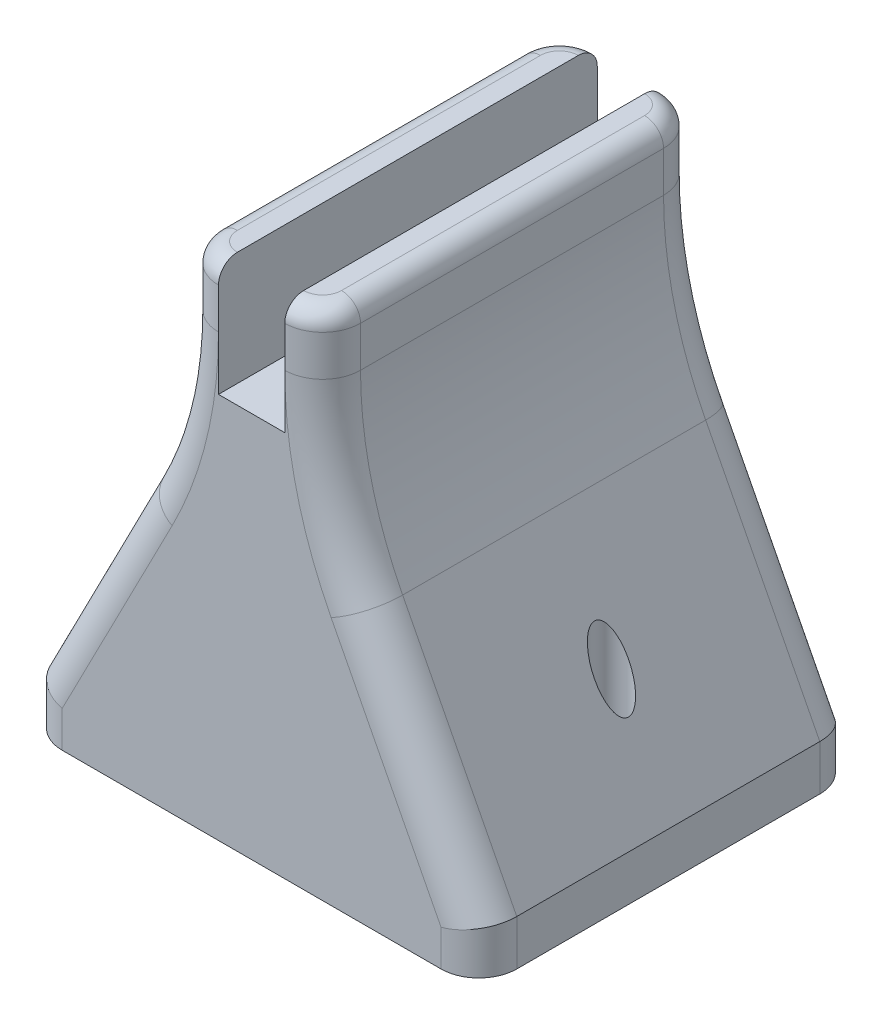
SolidWorks part; units mm, degrees
ref_plane "Front Plane" through (0, 0, 0) normal (0, 0, 1) x (1, 0, 0)
ref_plane "Top Plane" through (0, 0, 0) normal (0, 1, 0) x (1, 0, 0)
ref_plane "Right Plane" through (0, 0, 0) normal (1, 0, 0) x (0, 0, -1)
sketch "Sketch1" plane through (0, 0, 0) normal (0, 0, 1) x (1, 0, 0)
  line L0 (0, 0) -> (-37.5, 0)
  line L1 (-37.5, 0) -> (-37.5, 40)
  line L2 (-37.5, 40) -> (-27.5, 40)
  line L3 (-27.5, 40) -> (-27.5, 10)
  line L4 (-27.5, 10) -> (-10, 10)
  line L5 (-10, 10) -> (-10, 40)
  line L6 (-10, 40) -> (0, 40)
  line L7 (0, 40) -> (0, 0)
  dimension "D1" = 10
  dimension "D2" = 10
  dimension "D3" = 10
  dimension "D4" = 17.5
  dimension "D5" = 30
  dimension "D6" = 30
extrude "Boss-Extrude1" add sketch "Sketch1" along normal blind 100
sketch "Sketch2" plane through (0, 0, 0) normal (0, -1, 0) x (1, 0, 0)
  line L0 (-37.5, 100) -> (0, 0) construction
  line L1 (0, 100) -> (-37.5, 0) construction
  line L2 (-37.5, 100) -> (0, 100) construction
  line L3 (-78.75, 100) -> (41.25, 100)
  line L4 (-78.75, 100) -> (-78.75, 0)
  line L5 (-78.75, 0) -> (41.25, 0)
  line L6 (41.25, 100) -> (41.25, 0)
  line L7 (-78.75, 100) -> (41.25, 0) construction
  line L8 (-78.75, 0) -> (41.25, 100) construction
  point P8 (-18.75, 50)
  dimension "D1" = 0
  dimension "D2" = 120
extrude "Boss-Extrude2" add sketch "Sketch2" along normal blind 92
sketch "Sketch3" plane through (0, 0, 0) normal (0, 1, 0) x (1, 0, 0)
  line L0 (41.25, 0) -> (41.25, -100) construction
  line L1 (41.25, -100) -> (0, -100) construction
  line L2 (-37.5, -100) -> (-78.75, -100) construction
  line L3 (-78.75, -100) -> (-78.75, 0) construction
  circle A0 centre (26.25, -50) radius 4.5
  circle A1 centre (-63.75, -50) radius 4.5
  point P0 (26.25, -50)
  point P1 (-63.75, -50)
  dimension "D5" = 9
  dimension "D6" = 9
  dimension "D1" = 15
  dimension "D2" = 50
  dimension "D3" = 50
  dimension "D4" = 15
extrude "Cut-Extrude1" cut sketch "Sketch3" against normal blind 85
sketch "Sketch4" plane through (0, -85, 0) normal (0, 1, 0) x (1, 0, 0)
  circle A0 centre (26.25, -50) radius 2.65
  circle A1 centre (-63.75, -50) radius 2.65
  dimension "D1" = 5.3
  dimension "D2" = 5.3
extrude "Cut-Extrude2" cut sketch "Sketch4" against normal up to surface (7 mm away) up to face at (-18.75, -92, 50)
sketch "Sketch5" plane through (0, 0, 0) normal (0, 0, -1) x (-1, 0, 0)
  line L0 (0, 0) -> (-41.25, -80)
  line L1 (-41.25, -92) -> (-41.25, 0) construction
  line L2 (-41.25, -80) -> (-41.25, 0)
  line L3 (-41.25, 0) -> (0, 0)
  line L4 (37.5, 0) -> (78.75, 0)
  line L8 (78.75, 0) -> (78.75, -80)
  line L9 (78.75, -92) -> (78.75, 0) construction
  line L10 (78.75, -80) -> (37.5, 0)
  dimension "D1" = 41.25
  dimension "D2" = 41.25
  dimension "D3" = 80
  dimension "D4" = 80
extrude "Cut-Extrude3" cut sketch "Sketch5" against normal up to surface (100 mm away) up to face at (-18.75, -0.3333, 100)
fillet "Fillet1" radius 100 1 edges at (0, 0, 50) type face fillet first side face at (0, 20, 50) second side face at (20.625, -40, 50)
fillet "Fillet2" radius 100 1 edges at (-37.5, 0, 50) type face fillet first side face at (-37.5, 20, 50) second side face at (-58.125, -40, 50)
fillet "Fillet4" radius 10 16 edges at (-37.5, 32.1317, 100) (-40.3197, 0.6842, 100) (-37.5, 32.1317, 0) (-40.3197, 0.6842, 0) (-63.6848, -50.7827, 100) (-63.6848, -50.7827, 0) (0, 32.1317, 0) (2.8197, 0.6842, 0) (0, 32.1317, 100) (2.8197, 0.6842, 100) (26.1848, -50.7827, 0) (26.1848, -50.7827, 100) (41.25, -86, 0) (41.25, -86, 100) (-78.75, -86, 100) (-78.75, -86, 0)
fillet "Fillet5" radius 5 6 edges at (-2.9289, 40, 97.0711) (-2.9289, 40, 2.9289) (-34.5711, 40, 97.0711) (-34.5711, 40, 2.9289) (0, 40, 50) (-37.5, 40, 50)
